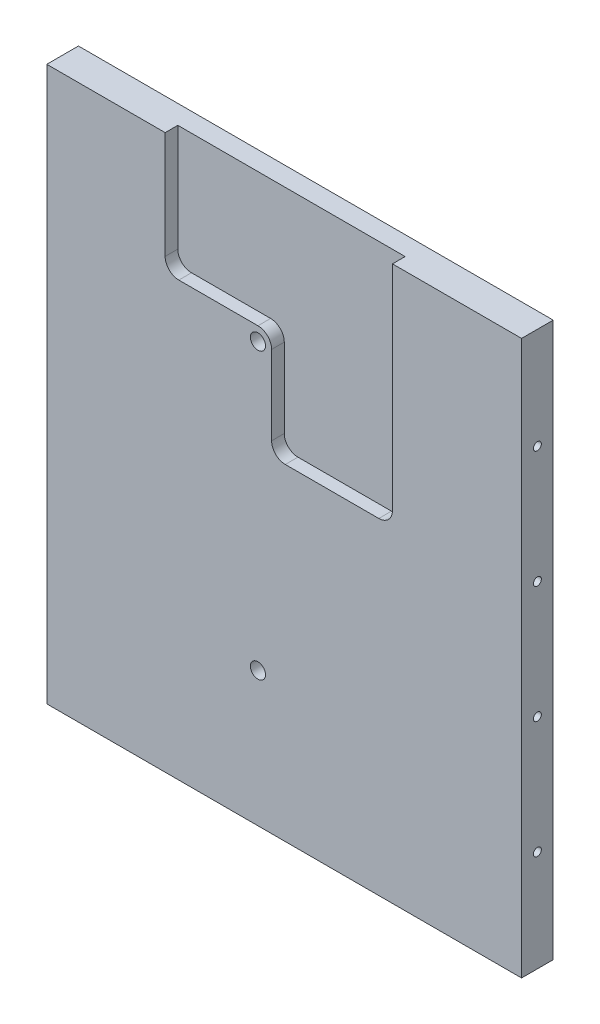
SolidWorks part; units mm, degrees
ref_plane "Ebene vorne" through (0, 0, 0) normal (0, 0, 1) x (1, 0, 0)
ref_plane "Ebene oben" through (0, 0, 0) normal (0, 1, 0) x (1, 0, 0)
ref_plane "Ebene rechts" through (0, 0, 0) normal (1, 0, 0) x (0, 0, -1)
sketch "Skizze1" plane through (0, 0, 0) normal (0, 0, 1) x (1, 0, 0)
  line L1 (-96.1409, 69.4002) -> (53.8591, 69.4002)
  line L2 (-96.1409, 69.4002) -> (-96.1409, -105.5998)
  line L3 (-96.1409, -105.5998) -> (53.8591, -105.5998)
  line L4 (53.8591, 69.4002) -> (53.8591, -105.5998)
  dimension "D1" = 150
  dimension "D2" = 175
extrude "Aufsatz-Linear austragen1" add sketch "Skizze1" along normal blind 10
sketch "Skizze2" plane through (0, 0, 10) normal (0, 0, 1) x (1, 0, 0)
  line L0 (-96.1409, -18.0998) -> (53.8591, -18.0998) construction
  line L1 (-96.1409, 69.4002) -> (-96.1409, -105.5998) construction
  line L2 (-96.1409, -18.0998) -> (33.5831, 69.4002) construction
  line L3 (53.8591, 69.4002) -> (-96.1409, 69.4002) construction
  line L4 (-96.1409, -18.0998) -> (33.5831, -105.5998) construction
  line L5 (-96.1409, -105.5998) -> (53.8591, -105.5998) construction
  line L6 (-29.4257, 26.9002) -> (53.8591, 26.9002) construction
  line L11 (53.8591, -105.5998) -> (53.8591, 69.4002) construction
  line L12 (-29.4257, -63.0998) -> (-29.4257, 26.9002) construction
  line L13 (53.8591, -8.0998) -> (-96.1409, -8.0998) construction
  line L14 (53.8591, -28.0998) -> (-96.1409, -28.0998) construction
  line L15 (-21.1409, -28.0998) -> (-21.1409, -8.0998) construction
  circle A0 centre (-29.4257, 26.9002) radius 2.3876
  circle A1 centre (-29.4257, -63.0998) radius 2.3876
  point P29 (-21.1409, -18.0998)
  dimension "D4" = 4.7752
  dimension "D6" = 4.7752
  dimension "D1" = 34
  dimension "D2" = 34
  dimension "D3" = 90
  dimension "D10" = 20
extrude "Schnitt-Linear austragen1" cut sketch "Skizze2" against normal blind 10
sketch "Skizze3" plane through (0, 0, 10) normal (0, 0, 1) x (1, 0, 0)
  line L1 (-54.4257, 31.2182) -> (-54.4257, 69.4002) construction
  line L7 (-54.4257, 31.2182) -> (-29.4257, 31.2182)
  line L8 (-25.1077, 26.9002) -> (-25.1077, 1.9002)
  line L9 (-20.7897, -2.4178) -> (8.7563, -2.4178)
  line L10 (13.0743, 1.9002) -> (13.0743, 69.4002)
  line L11 (53.8591, 69.4002) -> (-96.1409, 69.4002) construction
  line L12 (-58.7437, 35.5362) -> (-58.7437, 69.4002)
  line L13 (-58.7437, 69.4002) -> (13.0743, 69.4002)
  line L14 (-25.1077, 1.9002) -> (13.0743, 1.9002) construction
  arc A3 (-29.4257, 31.2182) -> (-25.1077, 26.9002) centre (-29.4257, 26.9002) cw
  arc A4 (-25.1077, 1.9002) -> (-20.7897, -2.4178) centre (-20.7897, 1.9002) ccw
  arc A5 (8.7563, -2.4178) -> (13.0743, 1.9002) centre (8.7563, 1.9002) ccw
  arc A6 (-54.4257, 31.2182) -> (-58.7437, 35.5362) centre (-54.4257, 35.5362) cw
  circle A7 centre (-29.4257, 26.9002) radius 2.3876 construction
  dimension "D1" = 4.318
  dimension "D2" = 25
  dimension "D3" = 25
extrude "Schnitt-Linear austragen2" cut sketch "Skizze3" against normal blind 4
sketch "Skizze4" plane through (-96.1409, 0, 0) normal (-1, 0, 0) x (0, 0, 1)
  line L0 (0, -18.0998) -> (10, -18.0998) construction
  line L1 (5, -36.5998) -> (5, 0.4002) construction
  line L2 (5, 0.4002) -> (5, 37.4002) construction
  line L3 (5, -36.5998) -> (5, -73.5998) construction
  line L4 (10, 69.4002) -> (10, -105.5998) construction
  line L5 (0, 69.4002) -> (0, -105.5998) construction
  circle A0 centre (5, 37.4002) radius 1.25
  circle A1 centre (5, 0.4002) radius 1.25
  circle A2 centre (5, -36.5998) radius 1.25
  circle A3 centre (5, -73.5998) radius 1.25
  point P4 (5, -18.0998)
  point P7 (5, -18.0998)
  point P12 (10, -18.0998)
  point P15 (0, -18.0998)
  dimension "D2" = 2.5
  dimension "D1" = 37
extrude "Schnitt-Linear austragen3" cut sketch "Skizze4" against normal blind 5
sketch "Skizze6" plane through (53.8591, 0, 0) normal (1, 0, 0) x (0, 0, -1)
  line L0 (-10, -18.0998) -> (0, -18.0998) construction
  line L1 (-5, -36.5998) -> (-5, 0.4002) construction
  line L2 (-5, 0.4002) -> (-5, 37.4002) construction
  line L3 (-5, -36.5998) -> (-5, -73.5998) construction
  line L4 (0, -105.5998) -> (0, 69.4002) construction
  line L5 (-10, -105.5998) -> (-10, 69.4002) construction
  circle A0 centre (-5, 37.4002) radius 1.25
  circle A1 centre (-5, 0.4002) radius 1.25
  circle A2 centre (-5, -36.5998) radius 1.25
  circle A3 centre (-5, -73.5998) radius 1.25
  point P4 (-5, -18.0998)
  point P7 (-5, -18.0998)
  point P12 (0, -18.0998)
  point P15 (-10, -18.0998)
  dimension "D2" = 2.5
  dimension "D1" = 37
extrude "Schnitt-Linear austragen4" cut sketch "Skizze6" against normal blind 5
